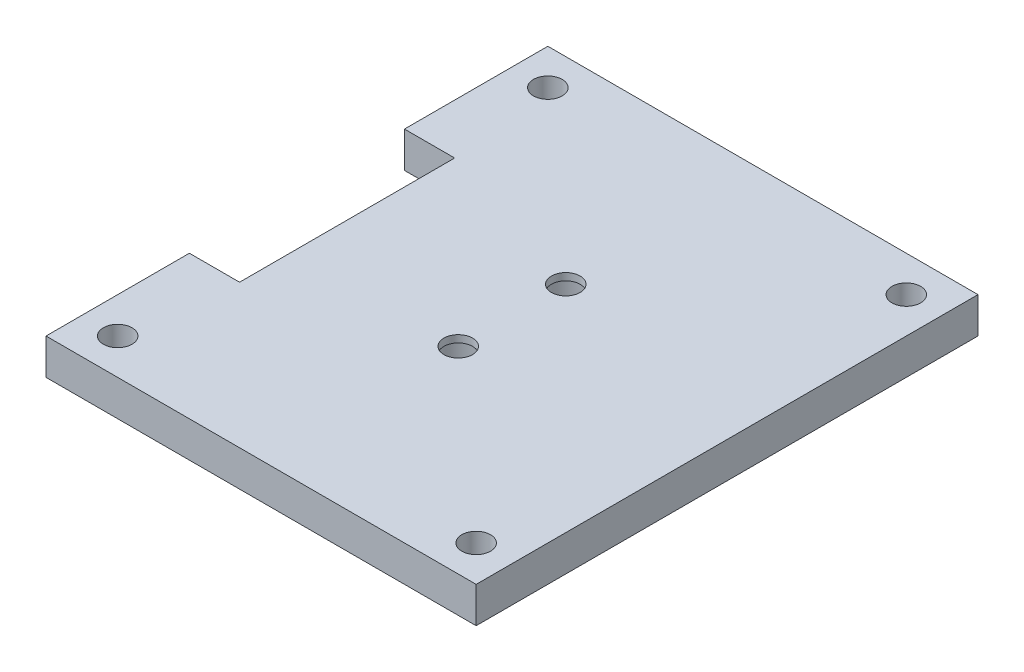
SolidWorks part; units mm, degrees
material "1060 Alloy"
ref_plane "Front Plane" through (0, 0, 0) normal (0, 0, 1) x (1, 0, 0)
ref_plane "Top Plane" through (0, 0, 0) normal (0, 1, 0) x (1, 0, 0)
ref_plane "Right Plane" through (0, 0, 0) normal (1, 0, 0) x (0, 0, -1)
sketch "Sketch1" plane through (0, 0, 0) normal (0, 1, 0) x (1, 0, 0)
  line L0 (-30, 15) -> (-30, -15)
  line L1 (-30, 35) -> (30, 35)
  line L2 (-30, 35) -> (-30, -35)
  line L3 (-30, -35) -> (30, -35)
  line L4 (30, 35) -> (30, -35)
  line L5 (-30, 35) -> (30, -35) construction
  line L6 (-30, -35) -> (30, 35) construction
  line L7 (-30, 15) -> (-23, 15)
  line L8 (-30, -15) -> (-23, -15)
  line L9 (-23, 15) -> (-23, -15)
  line L10 (-23, 0) -> (-30, 0) construction
  line L11 (-30, 0) -> (30, 0) construction
  circle A0 centre (-25, 30) radius 2
  circle A1 centre (25, 30) radius 2
  circle A2 centre (25, -30) radius 2
  circle A3 centre (-25, -30) radius 2
  point P0 (0, 0)
  point P23 (0, 0)
  dimension "D3" = 4
  dimension "D1" = 70
  dimension "D2" = 60
  dimension "D4" = 5
  dimension "D5" = 5
  dimension "D8" = 50
  dimension "D9" = 60
  dimension "D10" = 30
  dimension "D11" = 7
  dimension "D6" = 2
  dimension "D7" = 2
extrude "Boss-Extrude1" add sketch "Sketch1" along normal blind 5 contours L7 L9 L8 L2 L3 L4 L1 A3 A2 A1 A0 region at (1.4125, 0, 0)
sketch "Sketch3" plane through (0, 0, 0) normal (0, -1, 0) x (1, 0, 0)
  line L0 (0, 7.5) -> (0, -7.5) construction
  circle A0 centre (0, 7.5) radius 4
  circle A1 centre (0, -7.5) radius 4
  circle A2 centre (0, -7.5) radius 2
  circle A3 centre (0, 7.5) radius 2
  point P4 (0, 0)
  dimension "D2" = 8
  dimension "D3" = 8
  dimension "D4" = 4
  dimension "D5" = 4
  dimension "D1" = 15
extrude "Cut-Extrude1" cut sketch "Sketch3" against normal blind 4 contours A2 | A1 A2 | A3 A0 | A3 region at (-3.8869, 0, 7.5) region at (-3.8869, 0, -7.5) region at (0, 0, -7.5) region at (0, 0, 7.5)
extrude "Cut-Extrude2" cut sketch "Sketch3<4>" against normal through all contours A2 | A3 region at (0, 0, -7.5) region at (0, 0, 7.5)
sketch "Sketch3<4>" plane through (0, 0, 0) normal (0, -1, 0) x (1, 0, 0) same geometry as "Sketch3"
